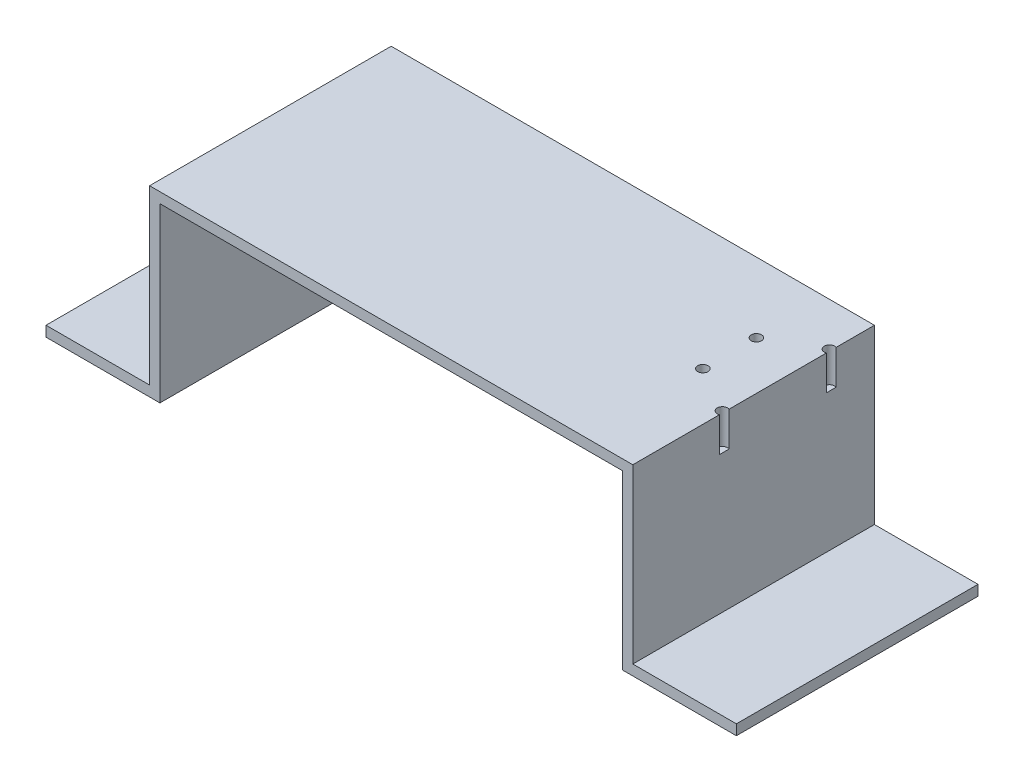
SolidWorks part; units mm, degrees
ref_plane "前视基准面" through (0, 0, 0) normal (0, 0, 1) x (1, 0, 0)
ref_plane "上视基准面" through (0, 0, 0) normal (0, 1, 0) x (1, 0, 0)
ref_plane "右视基准面" through (0, 0, 0) normal (1, 0, 0) x (0, 0, -1)
sketch "草图1" plane through (0, 0, 0) normal (0, 0, 1) x (1, 0, 0)
  line L0 (0, 0) -> (30, 0)
  line L1 (30, 0) -> (30, 50)
  line L2 (30, 50) -> (170, 50)
  line L3 (170, 50) -> (170, 0)
  line L4 (170, 0) -> (200, 0)
  line L5 (0, -3) -> (33, -3)
  line L6 (33, -3) -> (33, 47)
  line L7 (33, 47) -> (167, 47)
  line L8 (167, 47) -> (167, -3)
  line L9 (167, -3) -> (200, -3)
  line L10 (0, 0) -> (0, -3)
  line L11 (200, 0) -> (200, -3)
  dimension "D1" = 30
  dimension "D2" = 200
  dimension "D3" = 50
  dimension "D4" = 3
extrude "凸台-拉伸1" add sketch "草图1" along normal blind 70
sketch "草图2" plane through (0, 50, 0) normal (0, 1, 0) x (1, 0, 0)
  circle A0 centre (169.4682, -43.5) radius 1.5 construction
  circle A1 centre (182.8916, -35.75) radius 1.5 construction
  circle A2 centre (182.8916, -20.25) radius 1.5 construction
  circle A3 centre (169.4682, -12.5) radius 1.5 construction
  circle A4 centre (156.0448, -35.75) radius 1.5 construction
  circle A5 centre (156.0448, -20.25) radius 1.5 construction
  circle A6 centre (169.4682, -43.5) radius 1.5
  circle A7 centre (182.8916, -35.75) radius 1.5
  circle A8 centre (182.8916, -20.25) radius 1.5
  circle A9 centre (169.4682, -12.5) radius 1.5
  circle A10 centre (156.0448, -35.75) radius 1.5
  circle A11 centre (156.0448, -20.25) radius 1.5
extrude "切除-拉伸1" cut sketch "草图2" against normal blind 10
